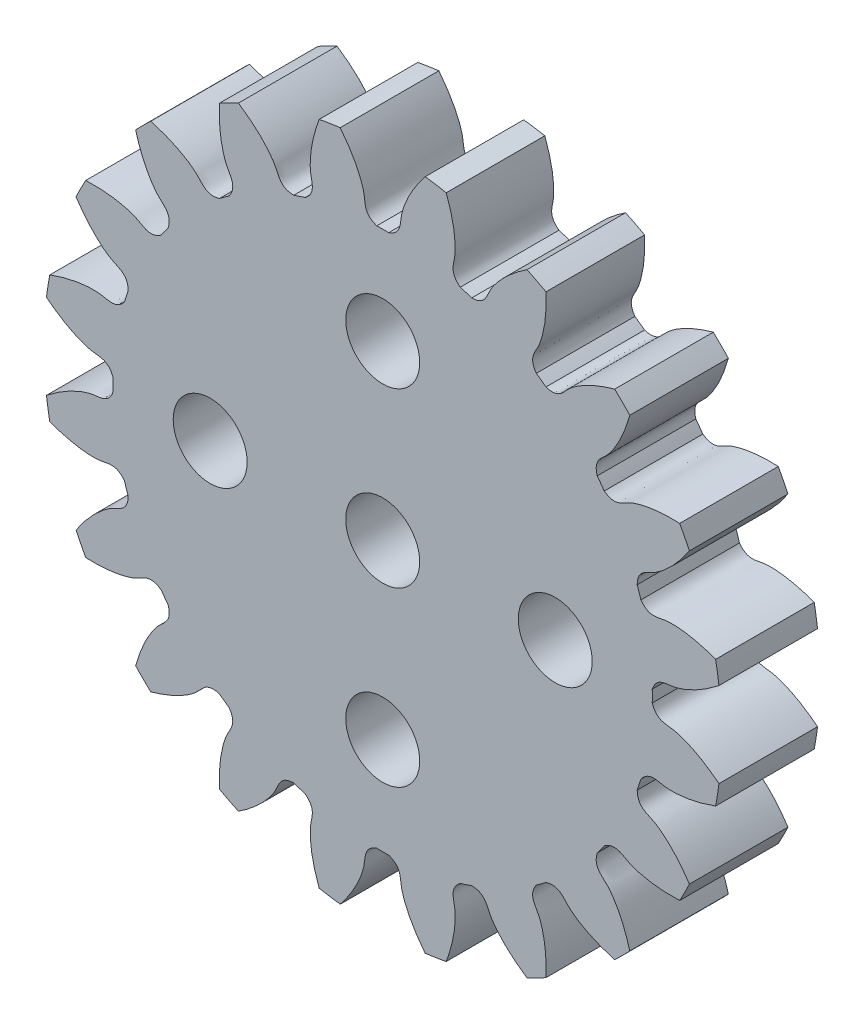
SolidWorks part; units mm, degrees
material "Thornel Mat VMA"
ref_plane "前视基准面" through (0, 0, 0) normal (0, 0, 1) x (1, 0, 0)
ref_plane "上视基准面" through (0, 0, 0) normal (0, 1, 0) x (1, 0, 0)
ref_plane "右视基准面" through (0, 0, 0) normal (1, 0, 0) x (0, 0, -1)
other "Configuration Table"
sketch "草图1" plane through (0, 0, 0) normal (0, 0, 1) x (1, 0, 0)
  circle A0 centre (0, 0) radius 13.75
extrude "凸台-拉伸1" add sketch "草图1" along normal blind 4
ref_axis "基准轴1" through (0, 0, -1.5) along (0, 0, 1)
sketch "草图2" plane through (0, 0, 0) normal (0, 0, 1) x (1, 0, 0)
  line L0 (0, 0) -> (0, 13.75) construction
  circle A0 centre (0, 0) radius 13.75 construction
  arc A1 (0.2416, 10.9348) -> (-0.2416, 10.9348) centre (0, 0) ccw
  arc A2 (3.9764, 15.6228) -> (-3.9764, 15.6228) centre (0, 0) ccw
  spline S0 degree 3 poles (0.2416, 10.9348) (0.764, 11.1168) (0.6964, 11.4839) (0.7661, 11.8375) (0.7736, 11.8719) (0.7829, 11.9108) (0.7941, 11.954) (0.8075, 12.0015) (0.8231, 12.0532) (0.8413, 12.1091) (0.8621, 12.169) (0.8857, 12.2329) (0.9123, 12.3007) (0.9421, 12.3723) (0.9752, 12.4476) (1.0117, 12.5264) (1.0519, 12.6088) (1.0959, 12.6945) (1.1438, 12.7834) (1.1957, 12.8755) (1.2519, 12.9705) (1.3125, 13.0684) (1.3775, 13.1691) (1.4472, 13.2723) (1.5216, 13.3779) (1.601, 13.4858) (1.6853, 13.5958) (1.7747, 13.7078) (1.8694, 13.8216) (1.9693, 13.937) (2.0748, 14.0539) (2.1857, 14.1721) (2.3023, 14.2914) (2.4246, 14.4116) (2.5527, 14.5326) (2.6866, 14.6542) (2.8265, 14.7761) (2.9725, 14.8983) (3.1245, 15.0204) (3.2826, 15.1424) (3.4469, 15.2639) (3.6768, 15.427) (3.8549, 15.5454) (3.9764, 15.6228) knots 0 0 0 0 0.165916 0.170906 0.176664 0.183189 0.190482 0.198542 0.207371 0.216967 0.22733 0.238462 0.250361 0.263027 0.276462 0.290664 0.305634 0.321371 0.337876 0.355149 0.37319 0.391998 0.411574 0.431917 0.453028 0.474907 0.497554 0.520968 0.54515 0.570099 0.595817 0.622302 0.649554 0.677575 0.706363 0.735918 0.766242 0.797333 0.829191 0.861818 0.895212 0.929373 1 1 1 1
  spline S1 degree 3 poles (-0.2416, 10.9348) (-0.764, 11.1168) (-0.6964, 11.4839) (-0.7661, 11.8375) (-0.7736, 11.8719) (-0.7829, 11.9108) (-0.7941, 11.954) (-0.8075, 12.0015) (-0.8231, 12.0532) (-0.8413, 12.1091) (-0.8621, 12.169) (-0.8857, 12.2329) (-0.9123, 12.3007) (-0.9421, 12.3723) (-0.9752, 12.4476) (-1.0117, 12.5264) (-1.0519, 12.6088) (-1.0959, 12.6945) (-1.1438, 12.7834) (-1.1957, 12.8755) (-1.2519, 12.9705) (-1.3125, 13.0684) (-1.3775, 13.1691) (-1.4472, 13.2723) (-1.5216, 13.3779) (-1.601, 13.4858) (-1.6853, 13.5958) (-1.7747, 13.7078) (-1.8694, 13.8216) (-1.9693, 13.937) (-2.0748, 14.0539) (-2.1857, 14.1721) (-2.3023, 14.2914) (-2.4246, 14.4116) (-2.5527, 14.5326) (-2.6866, 14.6542) (-2.8265, 14.7761) (-2.9725, 14.8983) (-3.1245, 15.0204) (-3.2826, 15.1424) (-3.4469, 15.2639) (-3.6768, 15.427) (-3.8549, 15.5454) (-3.9764, 15.6228) knots 0 0 0 0 0.165916 0.170906 0.176664 0.183189 0.190482 0.198542 0.207371 0.216967 0.22733 0.238462 0.250361 0.263027 0.276462 0.290664 0.305634 0.321371 0.337876 0.355149 0.37319 0.391998 0.411574 0.431917 0.453028 0.474907 0.497554 0.520968 0.54515 0.570099 0.595817 0.622302 0.649554 0.677575 0.706363 0.735918 0.766242 0.797333 0.829191 0.861818 0.895212 0.929373 1 1 1 1
extrude "切除-拉伸1" cut sketch "草图2" along normal through all
pattern_circular "阵列(圆周)1" count 20 every 18 about axis through (0, 0, -1.5) along (0, 0, 1) of "切除-拉伸1"
sketch "草图3" plane through (0, 0, 0) normal (0, 0, 1) x (1, 0, 0)
  circle A0 centre (0, 0) radius 12.5 construction
  dimension "Dn" = 25
sketch "草图4" plane through (0, 0, 4) normal (0, 0, 1) x (1, 0, 0)
  line L0 (0, 0) -> (0, 28.5084) construction
  line L1 (0, 0) -> (34.7245, 0) construction
  circle A0 centre (0, 0) radius 1.5
  circle A1 centre (0, 7) radius 1.5
  circle A2 centre (7, 0) radius 1.5
  circle A3 centre (-7, 0) radius 1.5
  circle A4 centre (0, -7) radius 1.5
  dimension "D1" = 3
  dimension "D2" = 3
  dimension "D3" = 3
  dimension "D4" = 7
  dimension "D5" = 7
extrude "切除-拉伸2" cut sketch "草图4" against normal blind 10
ref_axis "基准轴2" through (0, 0, -0.2) along (0, 0, 1)
